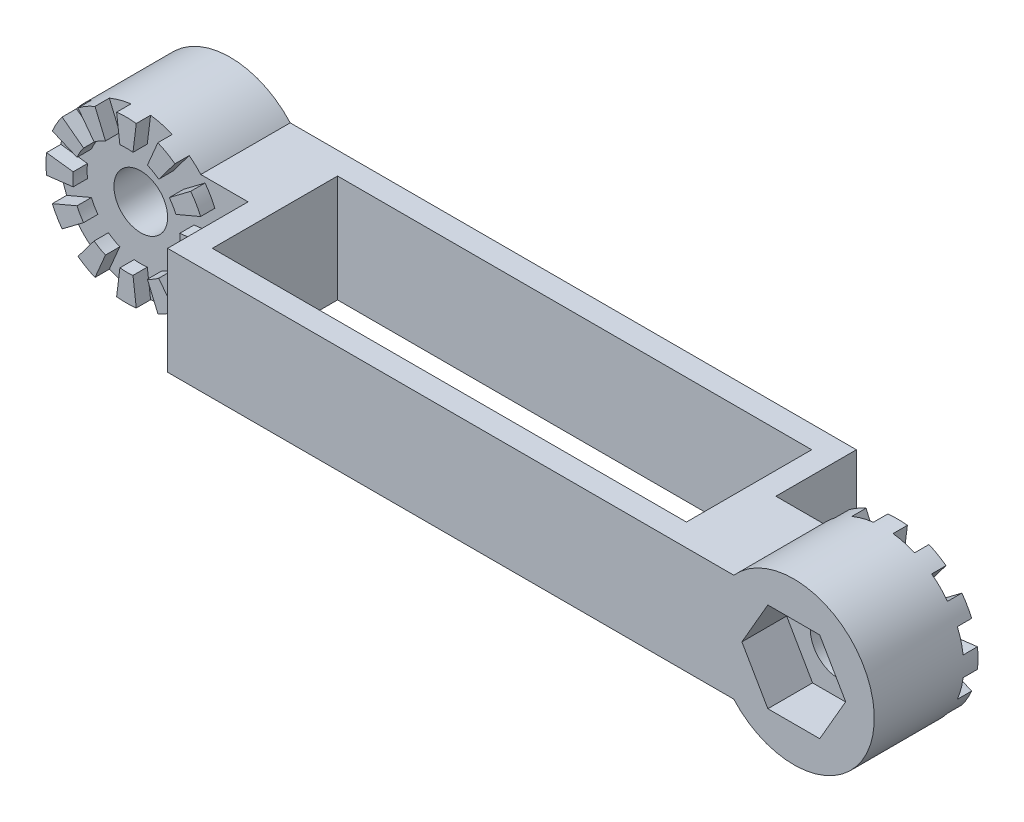
SolidWorks part; units mm, degrees
ref_plane "Alzado" through (0, 0, 0) normal (0, 0, 1) x (1, 0, 0)
ref_plane "Planta" through (0, 0, 0) normal (0, 1, 0) x (1, 0, 0)
ref_plane "Vista lateral" through (0, 0, 0) normal (1, 0, 0) x (0, 0, -1)
sketch "Croquis1" plane through (0, 0, 0) normal (0, 1, 0) x (1, 0, 0)
  line L0 (0, 0) -> (21, 0)
  line L1 (21, 0) -> (21, -9)
  line L2 (21, -9) -> (100, -9)
  line L3 (100, -9) -> (100, 1)
  line L4 (100, 1) -> (79, 1)
  line L5 (79, 1) -> (79, 10)
  line L6 (79, 10) -> (0, 10)
  line L7 (0, 10) -> (0, 0)
  line L8 (21, -9) -> (23.5, -9) construction
  line L9 (23.5, -6.5) -> (23.5, 7.5)
  line L10 (23.5, 7.5) -> (76.5, 7.5)
  line L11 (23.5, -6.5) -> (76.5, -6.5)
  line L12 (76.5, -6.5) -> (76.5, 7.5)
  dimension "D1" = 100
  dimension "D2" = 10
  dimension "D3" = 21
  dimension "D4" = 9
  dimension "D5" = 2.5
  dimension "D6" = 2.5
  dimension "D7" = 2.5
  dimension "D8" = 2.5
extrude "Saliente-Extruir1" add sketch "Croquis1" along normal blind 12
sketch "Croquis2" plane through (0, 0, 0) normal (0, 0, 1) x (1, 0, 0)
  line L0 (0, 6) -> (18, 6) construction
  line L1 (0, 12) -> (0, 0) construction
  circle A0 centre (9, 6) radius 9
  dimension "D1" = 18
extrude "Saliente-Extruir2" add sketch "Croquis2" against normal blind 10
sketch "Croquis3" plane through (0, 0, 0) normal (0, 0, 1) x (1, 0, 0)
  line L0 (0, 6) -> (9, 6) construction
  line L1 (0, 12) -> (0, 0) construction
  line L3 (9, 0.2) -> (14.0229, 3.1) construction
  line L4 (14.0229, 3.1) -> (14.0229, 8.9) construction
  line L5 (14.0229, 8.9) -> (9, 11.8) construction
  line L6 (9, 11.8) -> (3.9771, 8.9) construction
  line L7 (3.9771, 8.9) -> (3.9771, 3.1) construction
  line L8 (3.9771, 3.1) -> (9, 0.2) construction
  circle A0 centre (9, 6) radius 5.0229 construction
  circle A1 centre (9, 6) radius 3
  dimension "D3" = 9
  dimension "D4" = 6
  dimension "D1" = 5.8
  dimension "D2" = 5.8
sketch "Croquis4" plane through (0, 0, 9) normal (0, 0, 1) x (1, 0, 0)
  line L0 (100, 6) -> (91, 6) construction
  line L1 (100, 12) -> (100, 0) construction
  line L3 (96.8, 6) -> (93.9, 11.0229)
  line L4 (93.9, 11.0229) -> (88.1, 11.0229)
  line L5 (88.1, 11.0229) -> (85.2, 6)
  line L6 (85.2, 6) -> (88.1, 0.9771)
  line L7 (88.1, 0.9771) -> (93.9, 0.9771)
  line L8 (93.9, 0.9771) -> (96.8, 6)
  circle A0 centre (91, 6) radius 5.0229 construction
  dimension "D1" = 9
  dimension "D2" = 5.8
extrude "Cortar-Extruir3" cut sketch "Croquis4" against normal blind 5
sketch "Croquis5" plane through (0, 0, 4) normal (0, 0, 1) x (1, 0, 0)
  line L0 (85.2, 6) -> (96.8, 6) construction
  circle A0 centre (91, 6) radius 3.15
  dimension "D1" = 6.3
extrude "Cortar-Extruir4" cut sketch "Croquis5" against normal blind 10
sketch "Croquis6" plane through (0, 0, 9) normal (0, 0, 1) x (1, 0, 0)
  line L1 (96.8, 6) -> (93.9, 11.0229)
  line L2 (93.9, 11.0229) -> (88.1, 11.0229)
  line L3 (88.1, 11.0229) -> (85.2, 6)
  line L4 (85.2, 6) -> (88.1, 0.9771)
  line L5 (88.1, 0.9771) -> (93.9, 0.9771)
  line L6 (93.9, 0.9771) -> (96.8, 6)
  circle A0 centre (91, 6) radius 9
  circle A1 centre (91, 6) radius 5.0229 construction
  dimension "D1" = 18
  dimension "D2" = 5.8
extrude "Saliente-Extruir3" add sketch "Croquis6" against normal blind 10
extrude "Cortar-Extruir5" cut sketch "Croquis3" against normal blind 30
sketch "Croquis7" plane through (0, 0, 0) normal (0, 0, 1) x (1, 0, 0)
  line L0 (9, -3) -> (9, 15) construction
  line L1 (9, 6) -> (10.4937, 18.1654) construction
  line L2 (9, 6) -> (7.5063, 18.1654) construction
  line L3 (8.2688, 11.9553) -> (7.9032, 14.9329)
  line L4 (9.7312, 11.9553) -> (10.0968, 14.9329)
  line L5 (12.6109, 10.7918) -> (14.4163, 13.1877)
  line L6 (11.3444, 11.523) -> (12.5166, 14.2845)
  line L7 (14.523, 8.3444) -> (17.2845, 9.5166)
  line L8 (13.7918, 9.6109) -> (16.1877, 11.4163)
  line L9 (14.9553, 5.2688) -> (17.9329, 4.9032)
  line L10 (14.9553, 6.7312) -> (17.9329, 7.0968)
  line L11 (13.7918, 2.3891) -> (16.1877, 0.5837)
  line L12 (14.523, 3.6556) -> (17.2845, 2.4834)
  line L13 (11.3444, 0.477) -> (12.5166, -2.2845)
  line L14 (12.6109, 1.2082) -> (14.4163, -1.1877)
  line L15 (8.2688, 0.0447) -> (7.9032, -2.9329)
  line L16 (9.7312, 0.0447) -> (10.0968, -2.9329)
  line L17 (5.3891, 1.2082) -> (3.5837, -1.1877)
  line L18 (6.6556, 0.477) -> (5.4834, -2.2845)
  line L19 (3.477, 3.6556) -> (0.7155, 2.4834)
  line L20 (4.2082, 2.3891) -> (1.8123, 0.5837)
  line L21 (3.0447, 6.7312) -> (0.0671, 7.0968)
  line L22 (3.0447, 5.2688) -> (0.0671, 4.9032)
  line L23 (4.2082, 9.6109) -> (1.8123, 11.4163)
  line L24 (3.477, 8.3444) -> (0.7155, 9.5166)
  line L25 (6.6556, 11.523) -> (5.4834, 14.2845)
  line L26 (5.3891, 10.7918) -> (3.5837, 13.1877)
  line L27 (9, 6) -> (0, 6) construction
  line L28 (0, 12) -> (0, 0) construction
  line L29 (21, 12) -> (21, 0) construction
  line L30 (15.7082, 0) -> (21, 0) construction
  circle A0 centre (9, 6) radius 9 construction
  circle A1 centre (9, 6) radius 3 construction
  circle A2 centre (9, 6) radius 6 construction
  arc A3 (8.2688, 11.9553) -> (9.7312, 11.9553) centre (9, 6) cw
  arc A4 (7.9032, 14.9329) -> (10.0968, 14.9329) centre (9, 6) cw
  arc A5 (12.5166, 14.2845) -> (14.4163, 13.1877) centre (9, 6) cw
  arc A6 (11.3444, 11.523) -> (12.6109, 10.7918) centre (9, 6) cw
  arc A7 (16.1877, 11.4163) -> (17.2845, 9.5166) centre (9, 6) cw
  arc A8 (13.7918, 9.6109) -> (14.523, 8.3444) centre (9, 6) cw
  arc A9 (17.9329, 7.0968) -> (17.9329, 4.9032) centre (9, 6) cw
  arc A10 (14.9553, 6.7312) -> (14.9553, 5.2688) centre (9, 6) cw
  arc A11 (17.2845, 2.4834) -> (16.1877, 0.5837) centre (9, 6) cw
  arc A12 (14.523, 3.6556) -> (13.7918, 2.3891) centre (9, 6) cw
  arc A13 (14.4163, -1.1877) -> (12.5166, -2.2845) centre (9, 6) cw
  arc A14 (12.6109, 1.2082) -> (11.3444, 0.477) centre (9, 6) cw
  arc A15 (10.0968, -2.9329) -> (7.9032, -2.9329) centre (9, 6) cw
  arc A16 (9.7312, 0.0447) -> (8.2688, 0.0447) centre (9, 6) cw
  arc A17 (5.4834, -2.2845) -> (3.5837, -1.1877) centre (9, 6) cw
  arc A18 (6.6556, 0.477) -> (5.3891, 1.2082) centre (9, 6) cw
  arc A19 (1.8123, 0.5837) -> (0.7155, 2.4834) centre (9, 6) cw
  arc A20 (4.2082, 2.3891) -> (3.477, 3.6556) centre (9, 6) cw
  arc A21 (0.0671, 4.9032) -> (0.0671, 7.0968) centre (9, 6) cw
  arc A22 (3.0447, 5.2688) -> (3.0447, 6.7312) centre (9, 6) cw
  arc A23 (0.7155, 9.5166) -> (1.8123, 11.4163) centre (9, 6) cw
  arc A24 (3.477, 8.3444) -> (4.2082, 9.6109) centre (9, 6) cw
  arc A25 (3.5837, 13.1877) -> (5.4834, 14.2845) centre (9, 6) cw
  arc A26 (5.3891, 10.7918) -> (6.6556, 11.523) centre (9, 6) cw
  point P58 (17.0865, 28.4569)
  dimension "D1" = 18
  dimension "D2" = 6
  dimension "D4" = 12
  dimension "D3" = 7
extrude "Saliente-Extruir4" add sketch "Croquis7" along normal mid plane 3.2
sketch "Croquis8" plane through (0, 0, -1) normal (0, 0, -1) x (-1, 0, 0)
  line L0 (-91, 6) -> (-100, 6) construction
  line L1 (-100, 12) -> (-100, 0) construction
  line L2 (-91, -3) -> (-91, 15) construction
  line L3 (-91, 6) -> (-86.6189, 41.6809) construction
  line L4 (-91, 6) -> (-95.3811, 41.6809) construction
  line L5 (-91.7312, 11.9553) -> (-92.0968, 14.9329)
  line L6 (-90.2688, 11.9553) -> (-89.9032, 14.9329)
  line L7 (-87.3891, 10.7918) -> (-85.5837, 13.1877)
  line L8 (-88.6556, 11.523) -> (-87.4834, 14.2845)
  line L9 (-85.477, 8.3444) -> (-82.7155, 9.5166)
  line L10 (-86.2082, 9.6109) -> (-83.8123, 11.4163)
  line L11 (-85.0447, 5.2688) -> (-82.0671, 4.9032)
  line L12 (-85.0447, 6.7312) -> (-82.0671, 7.0968)
  line L13 (-86.2082, 2.3891) -> (-83.8123, 0.5837)
  line L14 (-85.477, 3.6556) -> (-82.7155, 2.4834)
  line L15 (-88.6556, 0.477) -> (-87.4834, -2.2845)
  line L16 (-87.3891, 1.2082) -> (-85.5837, -1.1877)
  line L17 (-91.7312, 0.0447) -> (-92.0968, -2.9329)
  line L18 (-90.2688, 0.0447) -> (-89.9032, -2.9329)
  line L19 (-94.6109, 1.2082) -> (-96.4163, -1.1877)
  line L20 (-93.3444, 0.477) -> (-94.5166, -2.2845)
  line L21 (-96.523, 3.6556) -> (-99.2845, 2.4834)
  line L22 (-95.7918, 2.3891) -> (-98.1877, 0.5837)
  line L23 (-96.9553, 6.7312) -> (-99.9329, 7.0968)
  line L24 (-96.9553, 5.2688) -> (-99.9329, 4.9032)
  line L25 (-95.7918, 9.6109) -> (-98.1877, 11.4163)
  line L26 (-96.523, 8.3444) -> (-99.2845, 9.5166)
  line L27 (-93.3444, 11.523) -> (-94.5166, 14.2845)
  line L28 (-94.6109, 10.7918) -> (-96.4163, 13.1877)
  circle A0 centre (-91, 6) radius 9 construction
  circle A1 centre (-91, 6) radius 3 construction
  circle A2 centre (-91, 6) radius 6 construction
  arc A3 (-91.7312, 11.9553) -> (-90.2688, 11.9553) centre (-91, 6) cw
  arc A4 (-92.0968, 14.9329) -> (-89.9032, 14.9329) centre (-91, 6) cw
  arc A5 (-87.4834, 14.2845) -> (-85.5837, 13.1877) centre (-91, 6) cw
  arc A6 (-88.6556, 11.523) -> (-87.3891, 10.7918) centre (-91, 6) cw
  arc A7 (-83.8123, 11.4163) -> (-82.7155, 9.5166) centre (-91, 6) cw
  arc A8 (-86.2082, 9.6109) -> (-85.477, 8.3444) centre (-91, 6) cw
  arc A9 (-82.0671, 7.0968) -> (-82.0671, 4.9032) centre (-91, 6) cw
  arc A10 (-85.0447, 6.7312) -> (-85.0447, 5.2688) centre (-91, 6) cw
  arc A11 (-82.7155, 2.4834) -> (-83.8123, 0.5837) centre (-91, 6) cw
  arc A12 (-85.477, 3.6556) -> (-86.2082, 2.3891) centre (-91, 6) cw
  arc A13 (-85.5837, -1.1877) -> (-87.4834, -2.2845) centre (-91, 6) cw
  arc A14 (-87.3891, 1.2082) -> (-88.6556, 0.477) centre (-91, 6) cw
  arc A15 (-89.9032, -2.9329) -> (-92.0968, -2.9329) centre (-91, 6) cw
  arc A16 (-90.2688, 0.0447) -> (-91.7312, 0.0447) centre (-91, 6) cw
  arc A17 (-94.5166, -2.2845) -> (-96.4163, -1.1877) centre (-91, 6) cw
  arc A18 (-93.3444, 0.477) -> (-94.6109, 1.2082) centre (-91, 6) cw
  arc A19 (-98.1877, 0.5837) -> (-99.2845, 2.4834) centre (-91, 6) cw
  arc A20 (-95.7918, 2.3891) -> (-96.523, 3.6556) centre (-91, 6) cw
  arc A21 (-99.9329, 4.9032) -> (-99.9329, 7.0968) centre (-91, 6) cw
  arc A22 (-96.9553, 5.2688) -> (-96.9553, 6.7312) centre (-91, 6) cw
  arc A23 (-99.2845, 9.5166) -> (-98.1877, 11.4163) centre (-91, 6) cw
  arc A24 (-96.523, 8.3444) -> (-95.7918, 9.6109) centre (-91, 6) cw
  arc A25 (-96.4163, 13.1877) -> (-94.5166, 14.2845) centre (-91, 6) cw
  arc A26 (-94.6109, 10.7918) -> (-93.3444, 11.523) centre (-91, 6) cw
  point P63 (-91, 6)
  dimension "D1" = 18
  dimension "D2" = 6
  dimension "D4" = 12
  dimension "D3" = 7
extrude "Saliente-Extruir5" add sketch "Croquis8" along normal mid plane 3.2
sketch "Croquis10" plane through (0, 0, -10) normal (0, 0, -1) x (-1, 0, 0)
  arc A0 (-9, 15) -> (-9, -3) centre (-9, 6) cw
  arc A1 (-2.2918, 12) -> (-15.7082, 12) centre (-9, 6) ccw construction
  arc A2 (-15.7082, 0) -> (-2.2918, 0) centre (-9, 6) ccw construction
  dimension "D1" = 9
extrude "Cortar-Extruir6" cut sketch "Croquis10" against normal blind 10 and the other way through all
sketch "Croquis11" plane through (0, 0, -1) normal (0, 0, -1) x (-1, 0, 0)
  arc A0 (-91, 15) -> (-91, -3) centre (-91, 6) ccw
  arc A1 (-89.9032, 14.9329) -> (-92.0968, 14.9329) centre (-91, 6) ccw construction
  arc A2 (-92.0968, -2.9329) -> (-89.9032, -2.9329) centre (-91, 6) ccw construction
  dimension "D1" = 9
extrude "Cortar-Extruir7" cut sketch "Croquis11" against normal blind 10 and the other way through all flip side to cut
